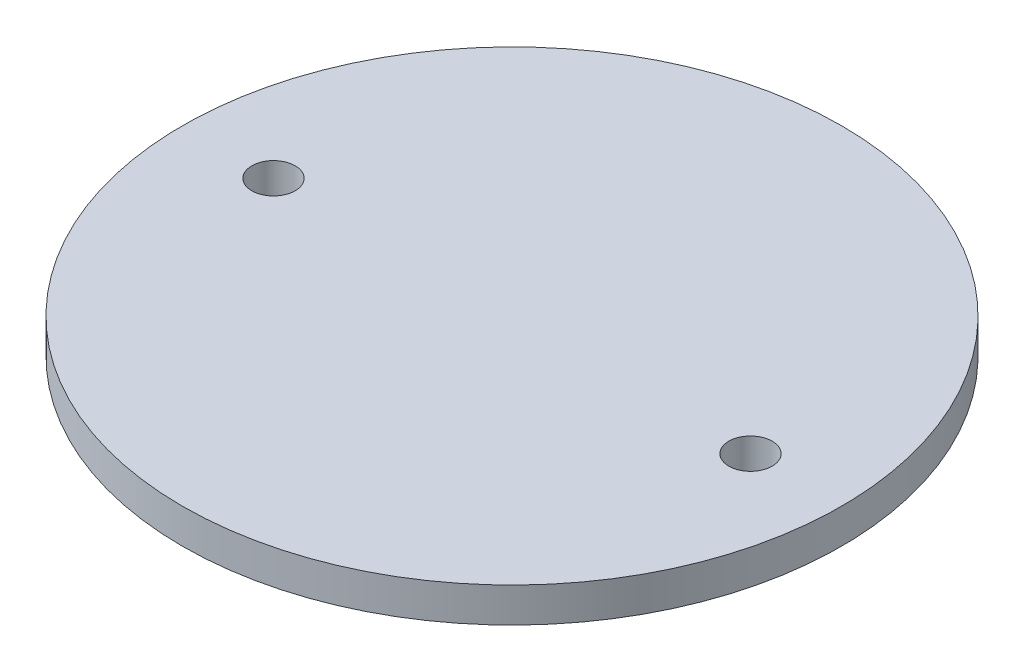
SolidWorks part; units mm, degrees
material "Balsa"
ref_plane "Front Plane" through (0, 0, 0) normal (0, 0, 1) x (1, 0, 0)
ref_plane "Top Plane" through (0, 0, 0) normal (0, 1, 0) x (1, 0, 0)
ref_plane "Right Plane" through (0, 0, 0) normal (1, 0, 0) x (0, 0, -1)
sketch "Sketch1" plane through (0, 0, 0) normal (0, 1, 0) x (1, 0, 0)
  line L0 (-38, 0) -> (38, 0) construction
  line L1 (0, 38) -> (0, -38) construction
  circle A0 centre (0, 0) radius 38
  circle A1 centre (-27.5, 0) radius 2.5
  circle A2 centre (27.5, 0) radius 2.5
  dimension "D1" = 55
  dimension "D2" = 76
  dimension "D3" = 5
extrude "Boss-Extrude1" add sketch "Sketch1" along normal blind 4
